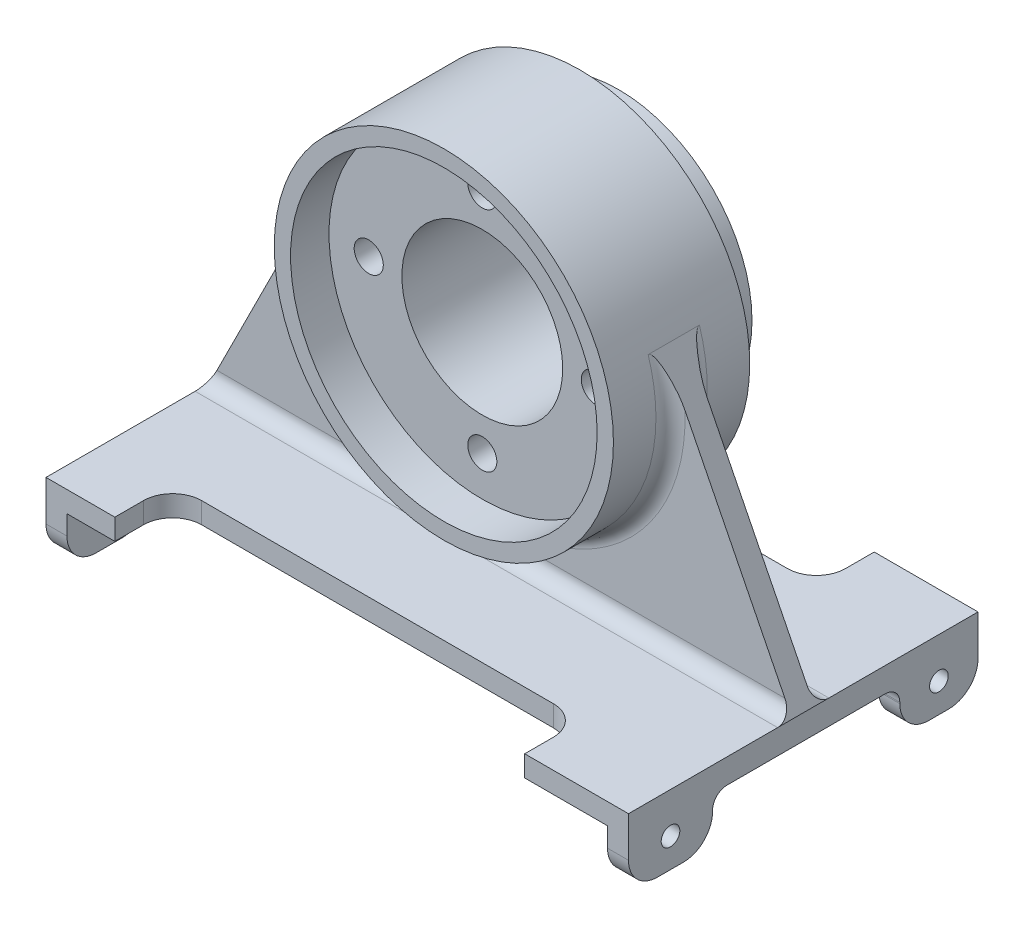
SolidWorks part; units mm, degrees
ref_plane "Front Plane" through (0, 0, 0) normal (0, 0, 1) x (1, 0, 0)
ref_plane "Top Plane" through (0, 0, 0) normal (0, 1, 0) x (1, 0, 0)
ref_plane "Right Plane" through (0, 0, 0) normal (1, 0, 0) x (0, 0, -1)
sketch "Sketch1" plane through (0, 0, 0) normal (0, 0, 1) x (1, 0, 0)
  line L0 (0, 0) -> (0, 15.148)
  line L1 (0, 15.148) -> (127, 15.148)
  line L2 (127, 15.148) -> (127, 0)
  line L3 (4.572, 0) -> (4.572, 10.576)
  line L4 (4.572, 10.576) -> (122.428, 10.576)
  line L5 (122.428, 10.576) -> (122.428, 0)
  line L6 (0, 0) -> (4.572, 0)
  line L7 (122.428, 0) -> (127, 0)
extrude "Extrude1" add sketch "Sketch1" against normal blind 76.2
ref_plane "Plane1" through (0, 15.148, 0) normal (0, 1, 0) x (-1, 0, 0)
sketch "Sketch2" plane through (0, 15.148, 0) normal (0, 1, 0) x (-1, 0, 0)
  line L0 (-63.5, 0) -> (-63.5, -76.2) construction
  line L1 (-127, 0) -> (0, 0) construction
  line L2 (-127, -76.2) -> (0, -76.2) construction
  line L3 (-15.009, 0) -> (-104.371, 0)
  line L4 (-63.5, -38.1) -> (-86.061, -38.1) construction
  line L5 (-15.009, 0) -> (-15.009, -6.2367)
  line L6 (-21.359, -12.5867) -> (-98.021, -12.5867)
  line L7 (-104.371, 0) -> (-104.371, -6.2367)
  line L8 (-104.371, -76.2) -> (-104.371, -69.9633)
  line L9 (-21.359, -63.6133) -> (-98.021, -63.6133)
  line L10 (-15.009, -76.2) -> (-15.009, -69.9633)
  line L11 (-15.009, -76.2) -> (-104.371, -76.2)
  arc A0 (-21.359, -12.5867) -> (-15.009, -6.2367) centre (-21.359, -6.2367) ccw
  arc A1 (-104.371, -6.2367) -> (-98.021, -12.5867) centre (-98.021, -6.2367) ccw
  arc A2 (-104.371, -69.9633) -> (-98.021, -63.6133) centre (-98.021, -69.9633) cw
  arc A3 (-21.359, -63.6133) -> (-15.009, -69.9633) centre (-21.359, -69.9633) cw
extrude "Extrude2" cut sketch "Sketch2" against normal blind 76.2
sketch "Sketch3" plane through (0, 0, 0) normal (1, 0, 0) x (0, 0, -1)
  line L0 (38.1, 0) -> (38.1, 15.1286) construction
  line L1 (76.2, 0) -> (0, 0) construction
  line L2 (18.3235, 0) -> (59.1465, 0)
  line L4 (18.3235, 0) -> (18.3235, 6.6236)
  line L5 (21.4985, 9.7986) -> (55.9715, 9.7986)
  line L6 (59.1465, 0) -> (59.1465, 6.6236)
  arc A0 (55.9715, 9.7986) -> (59.1465, 6.6236) centre (55.9715, 6.6236) cw
  arc A1 (18.3235, 6.6236) -> (21.4985, 9.7986) centre (21.4985, 6.6236) cw
  dimension "D1" = 3.175
extrude "Extrude3" cut sketch "Sketch3" along normal blind 159.766
fillet "Fillet2" radius 6.35 8 edges at (124.714, 0, 0) (2.286, 0, -18.3235) (2.286, 0, 0) (2.286, 0, -59.1465) (2.286, 0, -76.2) (124.714, 0, -76.2) (124.714, 0, -59.1465) (124.714, 0, -18.3235)
sketch "Sketch5" plane through (0, 0, 0) normal (1, 0, 0) x (0, 0, -1)
  circle A0 centre (67.6733, 6.35) radius 2.032
  circle A1 centre (9.1617, 6.35) radius 2.032
extrude "Extrude4" cut sketch "Sketch5" along normal blind 159.766
sketch "Sketch6" plane through (0, 15.148, 0) normal (0, 1, 0) x (-1, 0, 0)
  line L0 (0, -38.1) -> (-127, -38.1) construction
  line L1 (0, -76.2) -> (0, 0) construction
  line L2 (-127, -76.2) -> (-127, 0) construction
ref_plane "Plane3" through (0, 0, -38.1) normal (0, 0, 1) x (1, 0, 0)
sketch "Sketch7" plane through (0, 0, -38.1) normal (0, 0, 1) x (1, 0, 0)
  line L0 (0, 15.148) -> (127, 15.148) construction
  line L1 (63.5, 15.148) -> (63.5, 60.3747) construction
  circle A0 centre (63.5, 60.3747) radius 36.9728
extrude "Extrude5" add sketch "Sketch7" along normal mid plane 29.718 separate body
ref_plane "Plane4" through (0, 0, -52.959) normal (0, 0, -1) x (-1, 0, 0)
sketch "Sketch9" plane through (0, 0, -52.959) normal (0, 0, -1) x (-1, 0, 0)
  circle A2 centre (-63.5, 60.3747) radius 29.0871
extrude "Extrude7" add sketch "Sketch9" along normal blind 8.382
ref_plane "Plane5" through (0, 0, -23.241) normal (0, 0, 1) x (1, 0, 0)
sketch "Sketch10" plane through (0, 0, -23.241) normal (0, 0, 1) x (1, 0, 0)
  circle A2 centre (63.5, 60.3747) radius 33.4204
extrude "Extrude9" cut sketch "Sketch10" against normal blind 8.382
sketch "Sketch11" plane through (0, 0, -23.241) normal (0, 0, 1) x (1, 0, 0)
  circle A0 centre (63.5, 60.3747) radius 17.5324
extrude "Extrude10" cut sketch "Sketch11" against normal blind 85.598
ref_plane "Plane6" through (0, 0, -31.623) normal (0, 0, 1) x (1, 0, 0)
sketch "Sketch12" plane through (0, 0, -31.623) normal (0, 0, 1) x (1, 0, 0)
  line L0 (63.5, 60.3747) -> (88.2582, 60.3747) construction
  line L1 (63.5, 60.3747) -> (63.5, 35.6164) construction
  line L2 (63.5, 60.3747) -> (38.7418, 60.3747) construction
  line L3 (63.5, 60.3747) -> (63.5, 85.1329) construction
  circle A0 centre (63.5, 60.3747) radius 17.5324 construction
  circle A1 centre (63.5, 60.3747) radius 17.5324
hole_wizard "1/4-20 Tapped Hole1" positions "Sketch14" profile "Sketch13" tap size "1/4-20" standard "Ansi Inch"
sketch "Sketch14" plane through (0, 0, -31.623) normal (0, 0, 1) x (1, 0, 0)
  point P0 (38.7418, 60.3747)
  point P1 (63.5, 85.1329)
  point P4 (88.2582, 60.3747)
  point P7 (63.5, 35.6164)
sketch "Sketch13" plane through (38.7418, 60.3747, -31.623) normal (1, 0, 0) x (0, -1, 0)
  line L0 (0, 0) -> (0, 18.0438)
  line L1 (0, 18.0438) -> (2.5527, 16.51)
  line L2 (2.5527, 16.51) -> (2.5527, 12.7)
  line L3 (2.5527, 12.7) -> (3.175, 12.7)
  line L4 (3.175, 12.7) -> (3.175, 0)
  line L5 (3.175, 0) -> (0, 0)
  line L10 (0, 18.0438) -> (-2.5527, 16.51) construction
  line L11 (0, -6.35) -> (0, 107.95) construction
  dimension "Tap Drill Dia." = 5.1054
  dimension "Tap Drill Depth" = 16.51
  dimension "Thread Major Dia." = 6.35
  dimension "Thread Depth" = 12.7
  dimension "Drill Angle" = 118
sketch "Sketch15" plane through (0, 0, -38.1) normal (0, 0, 1) x (1, 0, 0)
  line L0 (0, 15.148) -> (28.228, 71.4596)
  line L1 (98.772, 71.4596) -> (96.4396, 71.4596)
  line L2 (0, 15.148) -> (127, 15.148) construction
  line L3 (36.5108, 38.8981) -> (63.5, 26.9543)
  line L4 (28.228, 71.4596) -> (30.2771, 71.4596)
  line L5 (98.772, 71.4596) -> (127, 15.148)
  line L6 (127, 15.148) -> (0, 15.148)
  line L7 (63.5, 26.9543) -> (89.1063, 38.8981)
  line L9 (30.2771, 71.4596) -> (36.5108, 38.8981)
  line L10 (96.4396, 71.4596) -> (89.1063, 38.8981)
  circle A0 centre (63.5, 60.3747) radius 36.9728 construction
  circle A1 centre (63.5, 60.3747) radius 33.4204 construction
  circle A2 centre (63.5, 60.3747) radius 33.4204 construction
extrude "Extrude11" add sketch "Sketch15" along normal mid plane 4.826
fillet "Fillet3" radius 3.175 5 edges at (63.5, 23.4019, -35.687) (28.228, 71.4596, -38.1) (63.5, 23.4019, -40.513)
